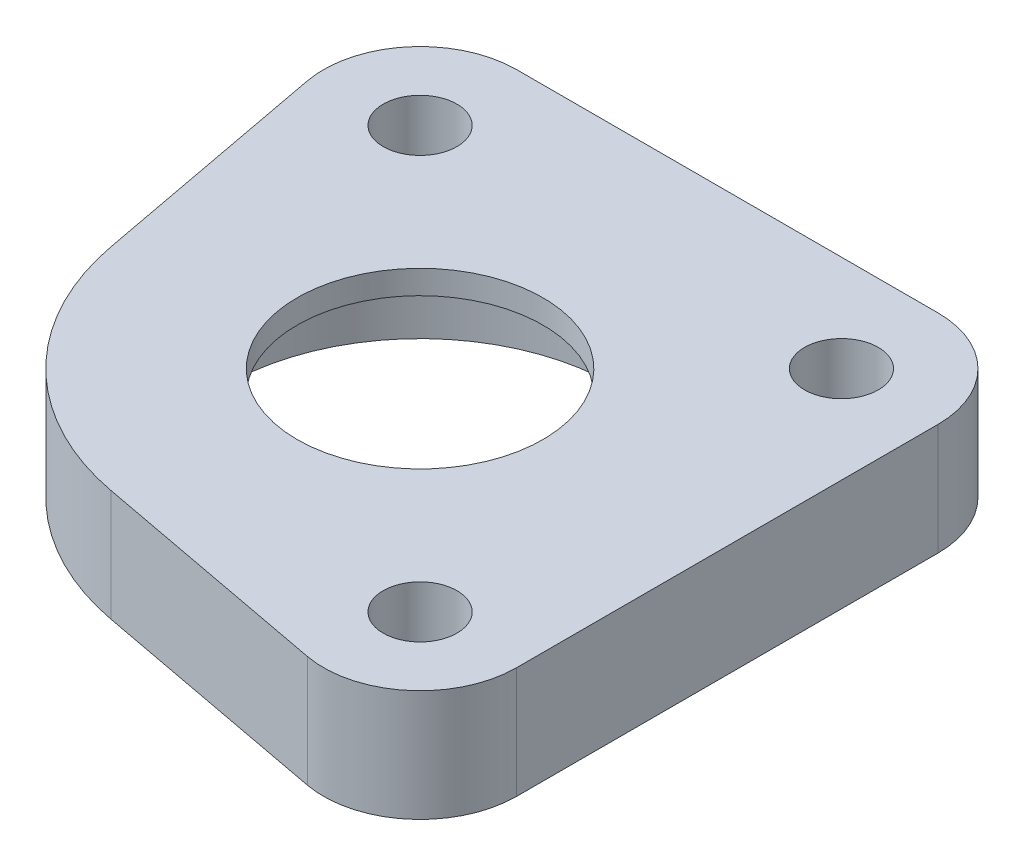
SolidWorks part; units mm, degrees
ref_plane "Front Plane" through (0, 0, 0) normal (0, 0, 1) x (1, 0, 0)
ref_plane "Top Plane" through (0, 0, 0) normal (0, 1, 0) x (1, 0, 0)
ref_plane "Right Plane" through (0, 0, 0) normal (1, 0, 0) x (0, 0, -1)
sketch "Sketch1" plane through (0, 0, 0) normal (0, 1, 0) x (1, 0, 0)
  line L0 (-12, 12) -> (0, 0) construction
  line L1 (0, 0) -> (12, 12) construction
  line L2 (0, 0) -> (0, 12) construction
  line L3 (-12, 12) -> (12, 12) construction
  line L4 (-12, 17.5) -> (12, 17.5)
  line L5 (17.5, 12) -> (17.5, -12)
  line L6 (-17.4052, 10.9833) -> (-14.8152, -2.7866)
  line L7 (10.9833, -17.4052) -> (-2.7866, -14.8152)
  circle A0 centre (0, 0) radius 11.075
  circle A1 centre (12, 12) radius 2.5 construction
  circle A2 centre (-12, 12) radius 2.5 construction
  circle A3 centre (12, -12) radius 2.5 construction
  arc A4 (-12, 17.5) -> (-17.4052, 10.9833) centre (-12, 12) ccw
  arc A5 (-14.8152, -2.7866) -> (-2.7866, -14.8152) centre (0, 0) ccw
  arc A6 (17.5, 12) -> (12, 17.5) centre (12, 12) ccw
  arc A7 (10.9833, -17.4052) -> (17.5, -12) centre (12, -12) ccw
  circle A8 centre (-12, 12) radius 5.5 construction
  circle A9 centre (0, 0) radius 15.075 construction
  circle A10 centre (12, -12) radius 5.5 construction
  circle A11 centre (12, 12) radius 5.5 construction
  circle A12 centre (0, 0) radius 7
  point P11 (0, 0)
  dimension "D1" = 22.15
  dimension "D2" = 5
  dimension "D6" = 14
  dimension "D3" = 12
  dimension "D4" = 12
  dimension "D7" = 4
  dimension "D8" = 3
  dimension "D5" = 3
extrude "Boss-Extrude1" add sketch "Sketch1" along normal blind 6.35 contours A4 L6 A5 L7 A7 L5 A6 L4 | A12
extrude "Cut-Extrude1" cut sketch "Sketch1<3>" along normal blind 5 contours A0
sketch "Sketch1<3>" plane through (0, 0, 0) normal (0, 1, 0) x (1, 0, 0) same geometry as "Sketch1"
sketch "Sketch2" plane through (0, 6.35, 0) normal (0, 1, 0) x (1, 0, 0)
  point P0 (-12, 12)
  point P2 (12, 12)
  point P4 (12, -12)
hole_wizard "M5x0.8 Tapped Hole1" positions "3DSketch1" profile "Sketch3" tap size "M5x0.8" standard "ANSI Metric" end condition through all
sketch3d "3DSketch1"
  point P0 (12, 6.35, -12)
  point P3 (12, 6.35, 12)
  point P6 (-12, 6.35, -12)
sketch "Sketch3" plane through (12, 6.35, -12) normal (1, 0, 0) x (0, 0, 1)
  line L0 (0, 0) -> (0, 6.35)
  line L1 (0, 6.35) -> (2.1, 6.35)
  line L2 (2.1, 6.35) -> (2.1, 0)
  line L5 (2.1, 0) -> (0, 0)
  line L11 (0, -6.35) -> (0, 107.95) construction
  dimension "Thru Tap Drill Dia." = 4.2
  dimension "Thru Tap Drill Depth" = 6.35
cosmetic thread "Hole Thread1" parameters "D2"=5
cosmetic thread "Hole Thread2" parameters "D2"=5
cosmetic thread "Hole Thread3" parameters "D2"=5
